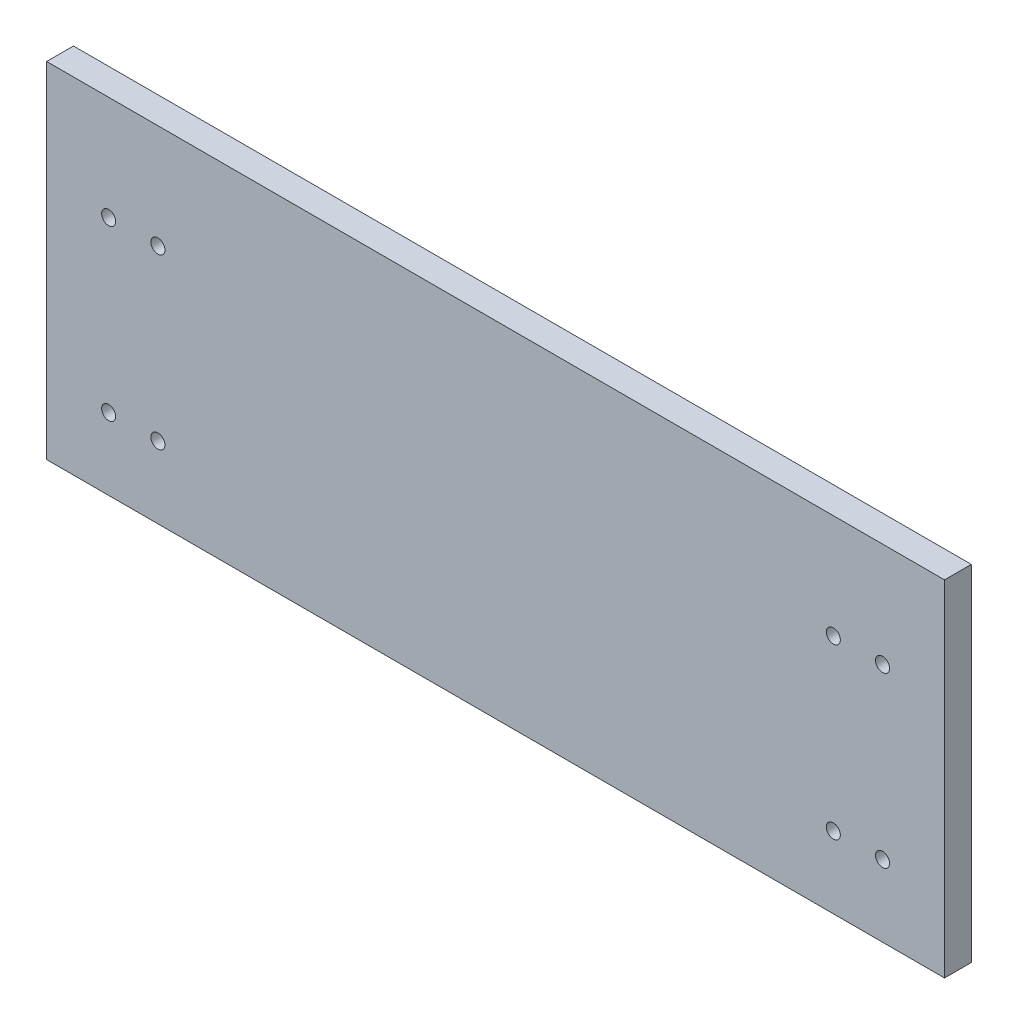
SolidWorks part; units mm, degrees
ref_plane "Front Plane" through (0, 0, 0) normal (0, 0, 1) x (1, 0, 0)
ref_plane "Top Plane" through (0, 0, 0) normal (0, 1, 0) x (1, 0, 0)
ref_plane "Right Plane" through (0, 0, 0) normal (1, 0, 0) x (0, 0, -1)
sketch "Sketch1" plane through (0, 0, 0) normal (0, 0, 1) x (1, 0, 0)
  line L1 (319.05, 19.05) -> (-319.05, 19.05)
  line L2 (319.05, 19.05) -> (319.05, -226)
  line L3 (319.05, -226) -> (-319.05, -226)
  line L4 (-319.05, 19.05) -> (-319.05, -226)
  dimension "D1" = 245.05
  dimension "D2" = 638.1
extrude "Boss-Extrude1" add sketch "Sketch1" along normal blind 19.05
sketch "Sketch5" plane through (0, 0, 19.05) normal (0, 0, 1) x (1, 0, 0)
  circle A0 centre (-275, -175) radius 9.017 construction
  circle A1 centre (-275, -55) radius 9.017 construction
  circle A2 centre (-240, -55) radius 9.017 construction
  circle A3 centre (-240, -175) radius 9.017 construction
  circle A4 centre (275, -55) radius 9.017 construction
  circle A5 centre (240, -55) radius 9.017 construction
  circle A6 centre (240, -175) radius 9.017 construction
  circle A7 centre (275, -175) radius 9.017 construction
  circle A8 centre (-275, -175) radius 9.017
  circle A9 centre (-275, -55) radius 9.017
  circle A10 centre (-240, -55) radius 9.017
  circle A11 centre (-240, -175) radius 9.017
  circle A12 centre (275, -55) radius 9.017
  circle A13 centre (240, -55) radius 9.017
  circle A14 centre (240, -175) radius 9.017
  circle A15 centre (275, -175) radius 9.017
hole_wizard "Ø10.0mm Dowel Hole1" positions "Sketch6" profile "Sketch7" hole size "Ø10.0" standard "ANSI Metric"
sketch "Sketch6" plane through (0, 0, 19.05) normal (0, 0, 1) x (1, 0, 0)
  point P0 (275, -175)
  point P3 (275, -55)
  point P6 (240, -175)
  point P9 (240, -55)
  point P12 (-275, -175)
  point P15 (-240, -175)
  point P18 (-240, -55)
  point P21 (-275, -55)
sketch "Sketch7" plane through (275, -175, 19.05) normal (1, 0, 0) x (0, -1, 0)
  line L0 (0, 0) -> (0, 30)
  line L1 (0, 30) -> (5, 26.9957)
  line L2 (5, 26.9957) -> (5, 0)
  line L5 (5, 0) -> (0, 0)
  line L10 (0, 30) -> (-5, 26.9957) construction
  line L11 (0, -6.35) -> (0, 107.95) construction
  dimension "Hole Dia." = 10
  dimension "Hole Depth" = 30
  dimension "Drill Angle" = 118
